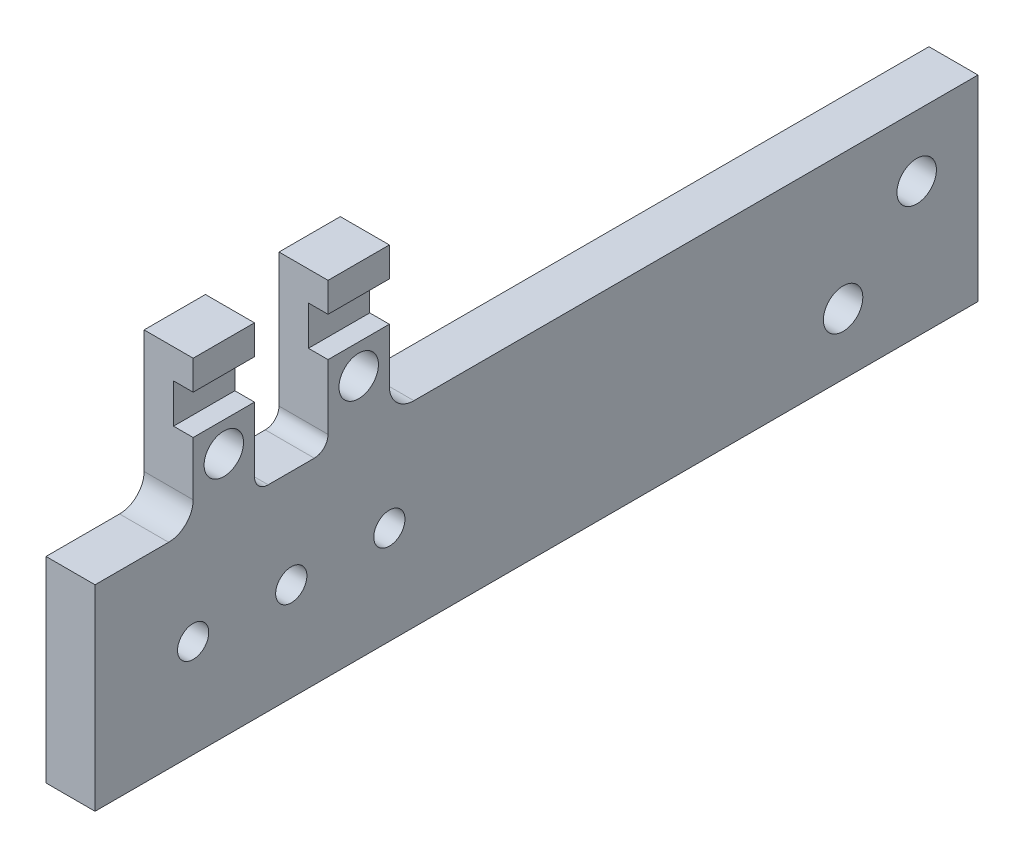
SolidWorks part; units mm, degrees
material "6061-T6 (SS)"
ref_plane "Front" through (0, 0, 0) normal (0, 0, 1) x (1, 0, 0)
ref_plane "Top" through (0, 0, 0) normal (0, 1, 0) x (1, 0, 0)
ref_plane "Right" through (0, 0, 0) normal (1, 0, 0) x (0, 0, -1)
sketch "Sketch1" plane through (0, 0, 0) normal (1, 0, 0) x (0, 0, -1)
  line L1 (0, 0) -> (114.3, 0)
  line L2 (0, 0) -> (0, 25.4)
  line L3 (0, 25.4) -> (9.525, 25.4)
  line L6 (114.3, 0) -> (114.3, 25.4)
  line L7 (38.1, 28.575) -> (38.1, 44.45)
  line L8 (38.1, 44.45) -> (30.1625, 44.45)
  line L9 (12.7, 44.45) -> (12.7, 28.575)
  line L10 (41.275, 25.4) -> (114.3, 25.4)
  line L11 (50.8, 25.4) -> (38.1, 44.45) construction
  line L12 (12.7, 44.45) -> (0, 25.4) construction
  line L14 (30.1625, 44.45) -> (30.1625, 27.178)
  line L15 (28.3845, 25.4) -> (22.4155, 25.4)
  line L16 (20.6375, 27.178) -> (20.6375, 44.45)
  line L17 (20.6375, 44.45) -> (12.7, 44.45)
  arc A0 (12.7, 28.575) -> (9.525, 25.4) centre (9.525, 28.575) cw
  arc A1 (38.1, 28.575) -> (41.275, 25.4) centre (41.275, 28.575) ccw
  arc A2 (22.4155, 25.4) -> (20.6375, 27.178) centre (22.4155, 27.178) cw
  arc A3 (30.1625, 27.178) -> (28.3845, 25.4) centre (28.3845, 27.178) cw
  point P14 (38.1, 25.4)
  dimension "D3" = 50.8
  dimension "D6" = 3.175
  dimension "D8" = 1.778
  dimension "D1" = 25.4
  dimension "D2" = 19.05
  dimension "D4" = 114.3
  dimension "D5" = 25.4
  dimension "D7" = 9.525
extrude "Boss-Extrude1" add sketch "Sketch1" along normal blind 6.35
hole_wizard "#10-32 Tapped Hole1" positions "Sketch2" profile "Sketch3" tap size "#10-32" standard "ANSI Inch" end condition through all
sketch "Sketch2" plane through (6.35, 0, 0) normal (1, 0, 0) x (0, 0, -1)
  line L0 (0, 0) -> (12.7, 12.7) construction
  line L1 (12.7, 12.7) -> (25.4, 12.7) construction
  line L2 (25.4, 12.7) -> (38.1, 12.7) construction
  line L3 (38.1, 12.7) -> (50.8, 25.4) construction
  line L4 (9.525, 25.4) -> (0, 25.4) construction
  line L6 (0, 25.4) -> (0, 0) construction
  point P0 (12.7, 12.7)
  point P2 (25.4, 12.7)
  point P4 (38.1, 12.7)
  dimension "D1" = 50.8
  dimension "D2" = 12.7
sketch "Sketch3" plane through (6.35, 12.7, -12.7) normal (0, 1, 0) x (0, 0, -1)
  line L0 (0, 0) -> (0, 6.35)
  line L1 (0, 6.35) -> (2.0193, 6.35)
  line L2 (2.0193, 6.35) -> (2.0193, 0)
  line L5 (2.0193, 0) -> (0, 0)
  line L11 (0, -6.35) -> (0, 107.95) construction
  dimension "Thru Tap Drill Dia." = 4.0386
  dimension "Thru Tap Drill Depth" = 6.35
cosmetic thread "Hole Thread1" parameters "D2"=4.826
cosmetic thread "Hole Thread2" parameters "D2"=4.826
cosmetic thread "Hole Thread3" parameters "D2"=4.826
hole_wizard "#10 Clearance Hole1" positions "Sketch4" profile "Sketch5" hole size "#10" standard "ANSI Inch" end condition through all
sketch "Sketch4" plane through (6.35, 0, 0) normal (1, 0, 0) x (0, 0, -1)
  line L0 (88.9, 0) -> (96.8375, 7.9375) construction
  line L1 (0, 0) -> (114.3, 0) construction
  line L2 (96.8375, 7.9375) -> (106.3625, 17.4625) construction
  line L3 (106.3625, 17.4625) -> (114.3, 25.4) construction
  line L5 (114.3, 0) -> (114.3, 25.4) construction
  line L6 (20.6375, 44.45) -> (16.6688, 31.75) construction
  line L7 (16.6688, 31.75) -> (12.7, 44.45) construction
  line L10 (30.1625, 44.45) -> (34.1313, 31.75) construction
  line L11 (34.1313, 31.75) -> (38.1, 44.45) construction
  line L13 (9.525, 25.4) -> (0, 25.4) construction
  point P13 (106.3625, 17.4625)
  point P15 (96.8375, 7.9375)
  point P37 (34.1313, 31.75)
  point P39 (16.6688, 31.75)
  dimension "D1" = 25.4
  dimension "D2" = 9.525
  dimension "D3" = 6.35
sketch "Sketch5" plane through (6.35, 17.4625, -106.3625) normal (0, 1, 0) x (0, 0, -1)
  line L0 (0, 0) -> (0, 6.35)
  line L1 (0, 6.35) -> (2.5527, 6.35)
  line L2 (2.5527, 6.35) -> (2.5527, 0)
  line L5 (2.5527, 0) -> (0, 0)
  line L11 (0, -6.35) -> (0, 107.95) construction
  dimension "Thru Hole Dia." = 5.1054
  dimension "Thru Hole Depth" = 6.35
sketch "Sketch6" plane through (6.35, 0, 0) normal (1, 0, 0) x (0, 0, -1)
  line L0 (12.7, 44.45) -> (12.7, 28.575) construction
  line L1 (12.7, 40.64) -> (38.1, 40.64)
  line L2 (12.7, 40.64) -> (12.7, 35.56)
  line L3 (12.7, 35.56) -> (38.1, 35.56)
  line L4 (38.1, 40.64) -> (38.1, 35.56)
  line L5 (38.1, 28.575) -> (38.1, 44.45) construction
  line L6 (9.525, 25.4) -> (0, 25.4) construction
  point P8 (12.7, 38.1)
  dimension "D1" = 5.08
  dimension "D2" = 12.7
extrude "Cut-Extrude1" cut sketch "Sketch6" against normal blind 2.54
